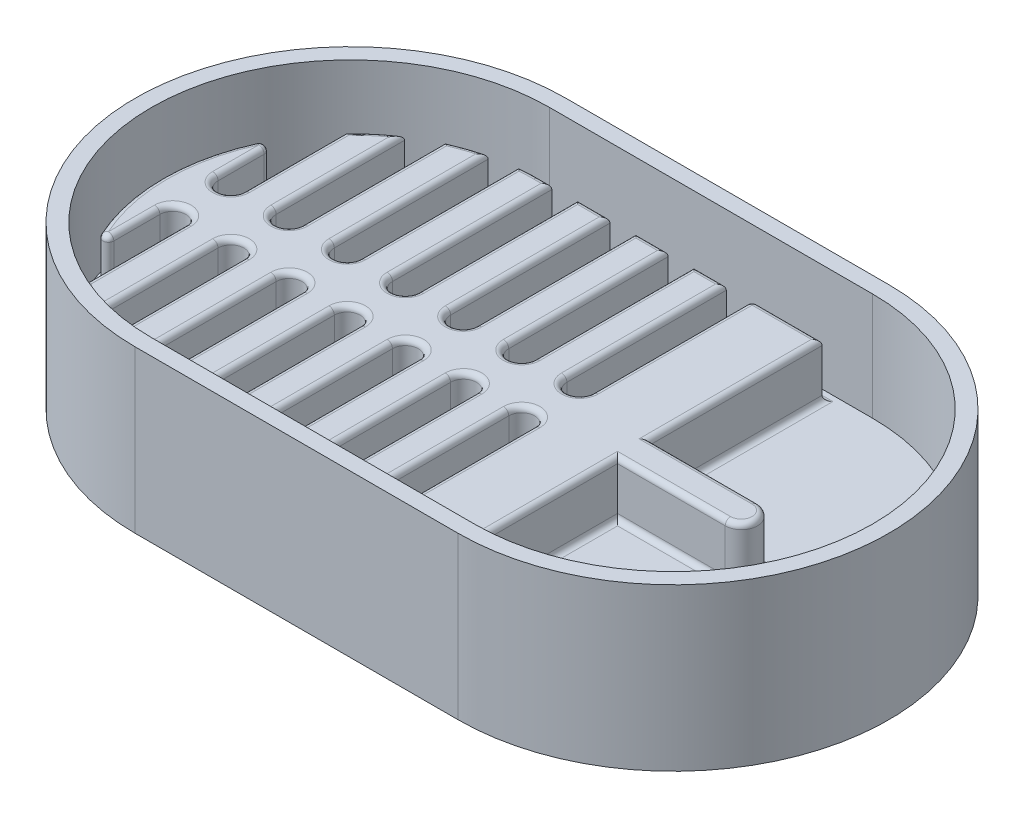
SolidWorks part; units mm, degrees
ref_plane "Front Plane" through (0, 0, 0) normal (0, 0, 1) x (1, 0, 0)
ref_plane "Top Plane" through (0, 0, 0) normal (0, 1, 0) x (1, 0, 0)
ref_plane "Right Plane" through (0, 0, 0) normal (1, 0, 0) x (0, 0, -1)
sketch "Sketch5" plane through (0, 0, 0) normal (0, 1, 0) x (1, 0, 0)
  line L0 (0, 0) -> (30, 0) construction
  line L1 (0, 20) -> (30, 20)
  line L2 (0, -20) -> (30, -20)
  line L12 (0, 0) -> (30, 0) construction
  line L25 (0, 18.5) -> (30, 18.5)
  line L26 (0, -18.5) -> (30, -18.5)
  line L27 (0, 0) -> (50000, 0) construction
  line L38 (0, -1.5) -> (50000, -1.5) construction
  line L39 (0, 1.5) -> (50000, 1.5) construction
  line L42 (-20, 0) -> (-20, 25.3424) construction
  line L43 (-15, 2.7) -> (-15, 9.0139)
  line L44 (-12.6, 2.7) -> (-12.6, 12.1445)
  line L45 (-9.6, 2.7) -> (-9.6, 14.6318)
  line L46 (-7.2, 2.7) -> (-7.2, 15.9502)
  line L48 (-4.2, 2.7) -> (-4.2, 16.9885)
  line L49 (-1.8, 2.7) -> (-1.8, 17.4072)
  line L52 (1.2, 2.7) -> (1.2, 17.5)
  line L53 (3.6, 2.7) -> (3.6, 17.5)
  line L54 (6.6, 2.7) -> (6.6, 17.5)
  line L56 (15.4, 18.5) -> (17.8, 18.5)
  line L57 (9, 2.7) -> (9, 17.5)
  line L59 (14.4, 2.7) -> (14.4, 17.5)
  line L60 (12, 2.7) -> (12, 17.5)
  line L61 (19.8, 2.7) -> (19.8, 17.5)
  line L62 (17.4, 2.7) -> (17.4, 17.5)
  line L63 (19.8, -2.7) -> (19.8, -17.5)
  line L64 (17.4, -2.7) -> (17.4, -17.5)
  line L65 (14.4, -2.7) -> (14.4, -17.5)
  line L66 (12, -2.7) -> (12, -17.5)
  line L67 (9, -2.7) -> (9, -17.5)
  line L68 (6.6, -2.7) -> (6.6, -17.5)
  line L69 (3.6, -2.7) -> (3.6, -17.5)
  line L71 (1.2, -2.7) -> (1.2, -17.5)
  line L72 (-1.8, -2.7) -> (-1.8, -17.4072)
  line L73 (-4.2, -2.7) -> (-4.2, -16.9885)
  line L74 (-7.2, -2.7) -> (-7.2, -15.9502)
  line L75 (-9.6, -2.7) -> (-9.6, -14.6318)
  line L76 (-15, -2.7) -> (-15, -9.0139)
  line L77 (-12.6, -2.7) -> (-12.6, -12.1445)
  line L82 (26.3, 17.5) -> (26.3, 1.5)
  line L83 (36.3, -1.5) -> (26.3, -1.5)
  line L84 (36.3, 1.5) -> (26.3, 1.5)
  line L85 (26.3, -1.5) -> (26.3, -17.5)
  line L86 (0, 17.5) -> (1.2, 17.5)
  line L87 (0, 17.5) -> (30, 17.5) construction
  line L88 (3.6, 17.5) -> (6.6, 17.5)
  line L89 (0, -17.5) -> (1.2, -17.5)
  line L90 (0, -17.5) -> (30, -17.5) construction
  line L91 (3.6, -17.5) -> (6.6, -17.5)
  line L92 (9, -17.5) -> (12, -17.5)
  line L93 (14.4, -17.5) -> (17.4, -17.5)
  line L94 (19.8, -17.5) -> (30, -17.5)
  line L95 (19.8, 17.5) -> (30, 17.5)
  line L96 (14.4, 17.5) -> (17.4, 17.5)
  line L97 (9, 17.5) -> (12, 17.5)
  line L98 (3.6, -17.5) -> (8, -17.5)
  arc A7 (0, 20) -> (0, -20) centre (0, 0) ccw
  arc A9 (30, -20) -> (30, 20) centre (30, 0) ccw
  arc A11 (0, 18.5) -> (0, -18.5) centre (0, 0) ccw
  arc A12 (30, -18.5) -> (30, 18.5) centre (30, 0) ccw
  arc A13 (-15, 2.7) -> (-12.6, 2.7) centre (-13.8, 2.7) ccw
  arc A14 (-9.6, 2.7) -> (-7.2, 2.7) centre (-8.4, 2.7) ccw
  arc A15 (-4.2, 2.7) -> (-1.8, 2.7) centre (-3, 2.7) ccw
  arc A16 (1.2, 2.7) -> (3.6, 2.7) centre (2.4, 2.7) ccw
  arc A17 (6.6, 2.7) -> (9, 2.7) centre (7.8, 2.7) ccw
  arc A18 (12, 2.7) -> (14.4, 2.7) centre (13.2, 2.7) ccw
  arc A19 (17.4, 2.7) -> (19.8, 2.7) centre (18.6, 2.7) ccw
  arc A20 (17.4, -2.7) -> (19.8, -2.7) centre (18.6, -2.7) cw
  arc A21 (12, -2.7) -> (14.4, -2.7) centre (13.2, -2.7) cw
  arc A22 (6.6, -2.7) -> (9, -2.7) centre (7.8, -2.7) cw
  arc A23 (1.2, -2.7) -> (3.6, -2.7) centre (2.4, -2.7) cw
  arc A24 (-4.2, -2.7) -> (-1.8, -2.7) centre (-3, -2.7) cw
  arc A25 (-9.6, -2.7) -> (-7.2, -2.7) centre (-8.4, -2.7) cw
  arc A26 (-15, -2.7) -> (-12.6, -2.7) centre (-13.8, -2.7) cw
  arc A29 (30, -17.5) -> (30, 17.5) centre (30, 0) ccw
  arc A30 (0, 17.5) -> (-1.8, 17.4072) centre (0, 0) ccw
  arc A31 (36.3, -1.5) -> (36.3, 1.5) centre (36.3, 0) ccw
  arc A32 (-15, 9.0139) -> (-15, -9.0139) centre (0, 0) ccw
  arc A33 (0, 17.5) -> (0, -17.5) centre (0, 0) ccw construction
  arc A34 (-9.6, 14.6318) -> (-12.6, 12.1445) centre (0, 0) ccw
  arc A35 (-12.6, -12.1445) -> (-9.6, -14.6318) centre (0, 0) ccw
  arc A36 (-7.2, -15.9502) -> (-4.2, -16.9885) centre (0, 0) ccw
  arc A37 (-1.8, -17.4072) -> (0, -17.5) centre (0, 0) ccw
  arc A38 (-4.2, 16.9885) -> (-7.2, 15.9502) centre (0, 0) ccw
  point P2 (15, 0)
  point P8 (15, 0)
  dimension "D2" = 20
  dimension "D3" = 18.5
  dimension "D6" = 2.4
  dimension "D8" = 2.4
  dimension "D10" = 2.4
  dimension "D11" = 2.4
  dimension "D14" = 2.4
  dimension "D4" = 1.5
  dimension "D5" = 1.5
  dimension "D7" = 5
  dimension "D9" = 3
  dimension "D12" = 3
  dimension "D13" = 3
  dimension "D15" = 3
  dimension "D16" = 3
  dimension "3" = 3
  dimension "D18" = 6.5
  dimension "D20" = 10
  dimension "D22" = 30
  dimension "D19" = 1
extrude "Boss-Extrude1" add sketch "Sketch5" along normal blind 10 contours L74 A36 L73 A24 L72 L89 L71 A23 L69 L91 L68 A22 L67 L92 L66 A21 L65 L93 L64 A20 L63 L94 L85 L83 A31 L84 L82 L95 L61 A19 L62 L96 L59 A18 L60 L97 L57 A17 L54 L88 L53 A16 L52 L86 L49 A15 L48 region at (8.1909, 0, 0)
extrude "Boss-Extrude2" add sketch "Sketch5<3>" along normal blind 5 contours A31 L83 L85 L94 A29 L95 L82 L84 | L26 A12 L25 A11 A36 L74 A25 L75 A35 L77 A26 L76 A32 L43 A13 L44 A34 L45 A14 L46 A30 L48 A15 L49 L86 L52 A16 L53 L88 L54 A17 L57 L97 L60 A18 L59 L96 L62 A19 L61 L95 A29 L94 L63 region at (7.7, 0, -17.7346) region at (28.15, 0, -17.0908)
sketch "Sketch5<3>" plane through (0, 0, 0) normal (0, 1, 0) x (1, 0, 0) same geometry as "Sketch5"
sketch "Sketch6" plane through (0, 5, 0) normal (0, 1, 0) x (1, 0, 0)
  line L0 (15.4, 18.5) -> (17.8, 18.5) construction
  line L1 (26.3, 17.5) -> (26.3, 1.5) construction
  line L2 (30, 18.5) -> (0, 18.5)
  line L3 (0, -18.5) -> (30, -18.5)
  line L4 (30, 18.5) -> (0, 18.5)
  line L5 (0, -18.5) -> (30, -18.5)
  line L6 (30, 20) -> (0, 20)
  line L7 (0, -20) -> (30, -20)
  line L8 (30, 20) -> (0, 20)
  line L9 (0, -20) -> (30, -20)
  line L10 (36.3, 1.5) -> (26.3, 1.5) construction
  line L11 (36.3, -1.5) -> (26.3, -1.5) construction
  line L12 (26.3, -1.5) -> (26.3, -17.5) construction
  line L13 (15.4, 18.5) -> (17.8, 18.5)
  line L14 (26.3, 17.5) -> (26.3, 1.5)
  line L15 (36.3, 1.5) -> (26.3, 1.5)
  line L16 (36.3, -1.5) -> (26.3, -1.5)
  line L17 (26.3, -1.5) -> (26.3, -17.5)
  line L50 (-12.6, 12.1445) -> (-12.6, 2.7)
  line L51 (-15, 2.7) -> (-15, 9.0139)
  line L52 (-15, -9.0139) -> (-15, -2.7)
  line L53 (-12.6, -2.7) -> (-12.6, -12.1445)
  line L54 (-9.6, -14.6318) -> (-9.6, -2.7)
  line L55 (-7.2, -2.7) -> (-7.2, -15.9502)
  line L57 (-4.2, -16.9885) -> (-4.2, -2.7)
  line L58 (-1.8, -2.7) -> (-1.8, -17.4072)
  line L59 (0, -17.5) -> (1.2, -17.5)
  line L61 (1.2, -17.5) -> (1.2, -2.7)
  line L62 (3.6, -2.7) -> (3.6, -17.5)
  line L63 (3.6, -17.5) -> (6.6, -17.5)
  line L64 (6.6, -17.5) -> (6.6, -2.7)
  line L65 (9, -2.7) -> (9, -17.5)
  line L66 (9, -17.5) -> (12, -17.5)
  line L67 (12, -17.5) -> (12, -2.7)
  line L68 (14.4, -2.7) -> (14.4, -17.5)
  line L69 (14.4, -17.5) -> (17.4, -17.5)
  line L70 (17.4, -17.5) -> (17.4, -2.7)
  line L71 (19.8, -2.7) -> (19.8, -17.5)
  line L72 (19.8, -17.5) -> (30, -17.5)
  line L73 (30, 17.5) -> (19.8, 17.5)
  line L74 (19.8, 17.5) -> (19.8, 2.7)
  line L75 (17.4, 2.7) -> (17.4, 17.5)
  line L76 (17.4, 17.5) -> (14.4, 17.5)
  line L77 (14.4, 17.5) -> (14.4, 2.7)
  line L78 (12, 2.7) -> (12, 17.5)
  line L79 (12, 17.5) -> (9, 17.5)
  line L80 (9, 17.5) -> (9, 2.7)
  line L81 (6.6, 2.7) -> (6.6, 17.5)
  line L82 (6.6, 17.5) -> (3.6, 17.5)
  line L83 (3.6, 17.5) -> (3.6, 2.7)
  line L84 (1.2, 2.7) -> (1.2, 17.5)
  line L86 (1.2, 17.5) -> (0, 17.5)
  line L87 (-1.8, 17.4072) -> (-1.8, 2.7)
  line L88 (-4.2, 2.7) -> (-4.2, 16.9885)
  line L90 (-7.2, 15.9502) -> (-7.2, 2.7)
  line L91 (-9.6, 2.7) -> (-9.6, 14.6318)
  line L92 (-12.6, 12.1445) -> (-12.6, 2.7)
  line L93 (-15, 2.7) -> (-15, 9.0139)
  line L94 (-15, -9.0139) -> (-15, -2.7)
  line L95 (-12.6, -2.7) -> (-12.6, -12.1445)
  line L96 (-9.6, -14.6318) -> (-9.6, -2.7)
  line L97 (-7.2, -2.7) -> (-7.2, -15.9502)
  line L99 (-4.2, -16.9885) -> (-4.2, -2.7)
  line L100 (-1.8, -2.7) -> (-1.8, -17.4072)
  line L101 (0, -17.5) -> (1.2, -17.5)
  line L103 (1.2, -17.5) -> (1.2, -2.7)
  line L104 (3.6, -2.7) -> (3.6, -17.5)
  line L105 (3.6, -17.5) -> (6.6, -17.5)
  line L106 (6.6, -17.5) -> (6.6, -2.7)
  line L107 (9, -2.7) -> (9, -17.5)
  line L108 (9, -17.5) -> (12, -17.5)
  line L109 (12, -17.5) -> (12, -2.7)
  line L110 (14.4, -2.7) -> (14.4, -17.5)
  line L111 (14.4, -17.5) -> (17.4, -17.5)
  line L112 (17.4, -17.5) -> (17.4, -2.7)
  line L113 (19.8, -2.7) -> (19.8, -17.5)
  line L114 (19.8, -17.5) -> (30, -17.5)
  line L115 (30, 17.5) -> (19.8, 17.5)
  line L116 (19.8, 17.5) -> (19.8, 2.7)
  line L117 (17.4, 2.7) -> (17.4, 17.5)
  line L118 (17.4, 17.5) -> (14.4, 17.5)
  line L119 (14.4, 17.5) -> (14.4, 2.7)
  line L120 (12, 2.7) -> (12, 17.5)
  line L121 (12, 17.5) -> (9, 17.5)
  line L122 (9, 17.5) -> (9, 2.7)
  line L123 (6.6, 2.7) -> (6.6, 17.5)
  line L124 (6.6, 17.5) -> (3.6, 17.5)
  line L125 (3.6, 17.5) -> (3.6, 2.7)
  line L126 (1.2, 2.7) -> (1.2, 17.5)
  line L128 (1.2, 17.5) -> (0, 17.5)
  line L129 (-1.8, 17.4072) -> (-1.8, 2.7)
  line L130 (-4.2, 2.7) -> (-4.2, 16.9885)
  line L132 (-7.2, 15.9502) -> (-7.2, 2.7)
  line L133 (-9.6, 2.7) -> (-9.6, 14.6318)
  arc A0 (36.3, -1.5) -> (36.3, 1.5) centre (36.3, 0) ccw construction
  arc A1 (36.3, -1.5) -> (36.3, 1.5) centre (36.3, 0) ccw
  arc A2 (30, -18.5) -> (30, 18.5) centre (30, 0) ccw
  arc A3 (0, 18.5) -> (0, -18.5) centre (0, 0) ccw
  arc A4 (30, -18.5) -> (30, 18.5) centre (30, 0) ccw
  arc A5 (0, 18.5) -> (0, -18.5) centre (0, 0) ccw
  arc A6 (30, -20) -> (30, 20) centre (30, 0) ccw
  arc A7 (0, 20) -> (0, -20) centre (0, 0) ccw
  arc A8 (30, -20) -> (30, 20) centre (30, 0) ccw
  arc A9 (0, 20) -> (0, -20) centre (0, 0) ccw
  arc A28 (-15, 2.7) -> (-12.6, 2.7) centre (-13.8, 2.7) ccw
  arc A29 (-15, 9.0139) -> (-15, -9.0139) centre (0, 0) ccw
  arc A30 (-12.6, -2.7) -> (-15, -2.7) centre (-13.8, -2.7) ccw
  arc A31 (-12.6, -12.1445) -> (-9.6, -14.6318) centre (0, 0) ccw
  arc A32 (-7.2, -2.7) -> (-9.6, -2.7) centre (-8.4, -2.7) ccw
  arc A33 (-7.2, -15.9502) -> (-4.2, -16.9885) centre (0, 0) ccw
  arc A34 (-1.8, -2.7) -> (-4.2, -2.7) centre (-3, -2.7) ccw
  arc A35 (3.6, -2.7) -> (1.2, -2.7) centre (2.4, -2.7) ccw
  arc A36 (9, -2.7) -> (6.6, -2.7) centre (7.8, -2.7) ccw
  arc A37 (14.4, -2.7) -> (12, -2.7) centre (13.2, -2.7) ccw
  arc A38 (19.8, -2.7) -> (17.4, -2.7) centre (18.6, -2.7) ccw
  arc A39 (30, -17.5) -> (30, 17.5) centre (30, 0) ccw
  arc A40 (17.4, 2.7) -> (19.8, 2.7) centre (18.6, 2.7) ccw
  arc A41 (12, 2.7) -> (14.4, 2.7) centre (13.2, 2.7) ccw
  arc A42 (6.6, 2.7) -> (9, 2.7) centre (7.8, 2.7) ccw
  arc A43 (1.2, 2.7) -> (3.6, 2.7) centre (2.4, 2.7) ccw
  arc A44 (-4.2, 2.7) -> (-1.8, 2.7) centre (-3, 2.7) ccw
  arc A45 (0, 17.5) -> (-1.8, 17.4072) centre (0, 0) ccw
  arc A46 (-9.6, 2.7) -> (-7.2, 2.7) centre (-8.4, 2.7) ccw
  arc A47 (-9.6, 14.6318) -> (-12.6, 12.1445) centre (0, 0) ccw
  arc A48 (-15, 2.7) -> (-12.6, 2.7) centre (-13.8, 2.7) ccw
  arc A49 (-15, 9.0139) -> (-15, -9.0139) centre (0, 0) ccw
  arc A50 (-12.6, -2.7) -> (-15, -2.7) centre (-13.8, -2.7) ccw
  arc A51 (-12.6, -12.1445) -> (-9.6, -14.6318) centre (0, 0) ccw
  arc A52 (-7.2, -2.7) -> (-9.6, -2.7) centre (-8.4, -2.7) ccw
  arc A53 (-7.2, -15.9502) -> (-4.2, -16.9885) centre (0, 0) ccw
  arc A54 (-1.8, -2.7) -> (-4.2, -2.7) centre (-3, -2.7) ccw
  arc A55 (3.6, -2.7) -> (1.2, -2.7) centre (2.4, -2.7) ccw
  arc A56 (9, -2.7) -> (6.6, -2.7) centre (7.8, -2.7) ccw
  arc A57 (14.4, -2.7) -> (12, -2.7) centre (13.2, -2.7) ccw
  arc A58 (19.8, -2.7) -> (17.4, -2.7) centre (18.6, -2.7) ccw
  arc A59 (30, -17.5) -> (30, 17.5) centre (30, 0) ccw
  arc A60 (17.4, 2.7) -> (19.8, 2.7) centre (18.6, 2.7) ccw
  arc A61 (12, 2.7) -> (14.4, 2.7) centre (13.2, 2.7) ccw
  arc A62 (6.6, 2.7) -> (9, 2.7) centre (7.8, 2.7) ccw
  arc A63 (1.2, 2.7) -> (3.6, 2.7) centre (2.4, 2.7) ccw
  arc A64 (-4.2, 2.7) -> (-1.8, 2.7) centre (-3, 2.7) ccw
  arc A65 (0, 17.5) -> (-1.8, 17.4072) centre (0, 0) ccw
  arc A66 (-9.6, 2.7) -> (-7.2, 2.7) centre (-8.4, 2.7) ccw
  arc A67 (-9.6, 14.6318) -> (-12.6, 12.1445) centre (0, 0) ccw
  arc A72 (-1.8, -17.4072) -> (0, -17.5) centre (0, 0) ccw
  arc A73 (-1.8, -17.4072) -> (0, -17.5) centre (0, 0) ccw
  arc A74 (-4.2, 16.9885) -> (-7.2, 15.9502) centre (0, 0) ccw
  arc A75 (-4.2, 16.9885) -> (-7.2, 15.9502) centre (0, 0) ccw
  dimension "D1" = 0
  dimension "D2" = 0
  dimension "D3" = 0
extrude "Boss-Extrude4" add sketch "Sketch6" along normal blind 10 separate body contours L8 A9 L9 A8 A5 L4 A4 L5 region at (49.1938, 5, 0)
extrude "Boss-Extrude5" add sketch "Sketch6<4>" against normal up to surface (5 mm away) contours A9 L9 A8 L8 up to face at (15, 0, 0)
sketch "Sketch6<4>" plane through (0, 5, 0) normal (0, 1, 0) x (1, 0, 0) same geometry as "Sketch6"
ref_plane "Plane6" through (30, 15, -20) normal (0, 1, 0) x (1, 0, 0)
fillet "Fillet1" radius 0.5 116 edges at (23.05, 5, -17.5) (1.2, 5, 10.1) (3.6, 5, 10.1) (17.4, 5, -10.1) (18.6, 5, -1.5) (6.6, 5, 10.1) (9, 5, 10.1) (-4.2, 5, 9.8443) (-1.8, 5, 10.0536) (-9.6, 5, 8.6659) (-7.2, 5, 9.3251) (-15, 5, 5.8569) (-12.6, 5, 7.4223) (-15, 5, -5.8569) (-12.6, 5, -7.4223) (-9.6, 5, -8.6659) (-7.2, 5, -9.3251) (-4.2, 5, -9.8443) (-1.8, 5, -10.0536) (1.2, 5, -10.1) (3.6, 5, -10.1) (6.6, 5, -10.1) (9, 5, -10.1) (12, 5, -10.1) (14.4, 5, -10.1) (12, 5, 10.1) (14.4, 5, 10.1) (17.4, 5, 10.1) (18.6, 5, 1.5) (31.3, 5, 1.5) (31.3, 5, -1.5) (-15, 7.5, 9.0139) (-17.5, 5, 0) (-15, 7.5, -9.0139) (2.4, 5, 1.5) (19.8, 7.5, -17.5) (19.8, 5, -10.1) (-3, 10, -1.5) (-1.8, 10, -10.0536) (-0.9012, 10, -17.4768) (0.6, 10, -17.5) (1.2, 10, -10.1) (2.4, 10, -1.5) (3.6, 10, -10.1) (5.1, 10, -17.5) (6.6, 10, -10.1) (7.8, 10, -1.5) (9, 10, -10.1) (10.5, 10, -17.5) (12, 10, -10.1) (13.2, 10, -1.5) (14.4, 10, -10.1) (15.9, 10, -17.5) (17.4, 10, -10.1) (18.6, 10, -1.5) (19.8, 10, -10.1) (23.05, 10, -17.5) (26.3, 10, -9.5) (31.3, 10, -1.5) (37.8, 10, 0) (31.3, 10, 1.5) (26.3, 10, 9.5) (23.05, 10, 17.5) (19.8, 10, 10.1) (18.6, 10, 1.5) (17.4, 10, 10.1) (15.9, 10, 17.5) (14.4, 10, 10.1) (13.2, 10, 1.5) (12, 10, 10.1) (10.5, 10, 17.5) (9, 10, 10.1) (7.8, 10, 1.5) (6.6, 10, 10.1) (5.1, 10, 17.5) (3.6, 10, 10.1) (2.4, 10, 1.5) (1.2, 10, 10.1) (0.6, 10, 17.5) (-0.9012, 10, 17.4768) (-1.8, 10, 10.0536) (-3, 10, 1.5) (-4.2, 10, 9.8443) (-5.7236, 10, 16.5375) (-7.2, 10, 9.3251) (-8.4, 10, 1.5) (-9.6, 10, 8.6659) (-11.1695, 10, 13.4719) (-12.6, 10, 7.4223) (-13.8, 10, 1.5) (-15, 10, 5.8569) (-17.5, 10, 0) (-15, 10, -5.8569) (-13.8, 10, -1.5) (-12.6, 10, -7.4223) (-11.1695, 10, -13.4719) (-9.6, 10, -8.6659) (-8.4, 10, -1.5) (-7.2, 10, -9.3251) (-5.7236, 10, -16.5375) (-4.2, 10, -9.8443) (7.8, 5, 1.5) (-3, 5, 1.5) (-8.4, 5, 1.5) (-13.8, 5, 1.5) (-13.8, 5, -1.5) (-8.4, 5, -1.5) (-3, 5, -1.5) (2.4, 5, -1.5) (7.8, 5, -1.5) (13.2, 5, -1.5) (13.2, 5, 1.5) (19.8, 5, 10.1) (37.8, 5, 0) (26.3, 5, -9.5) (26.3, 5, 9.5)
equation "\"b\"= 50mm"
equation "\"height\"= 10mm"
equation "\"t\"= 1.5mm"
equation "\"n\"= 7"
equation "\"t_rib\"= 3mm"
equation "\"t_air\"= 10mm"
equation "\"t_mold\"= 2.4mm"
